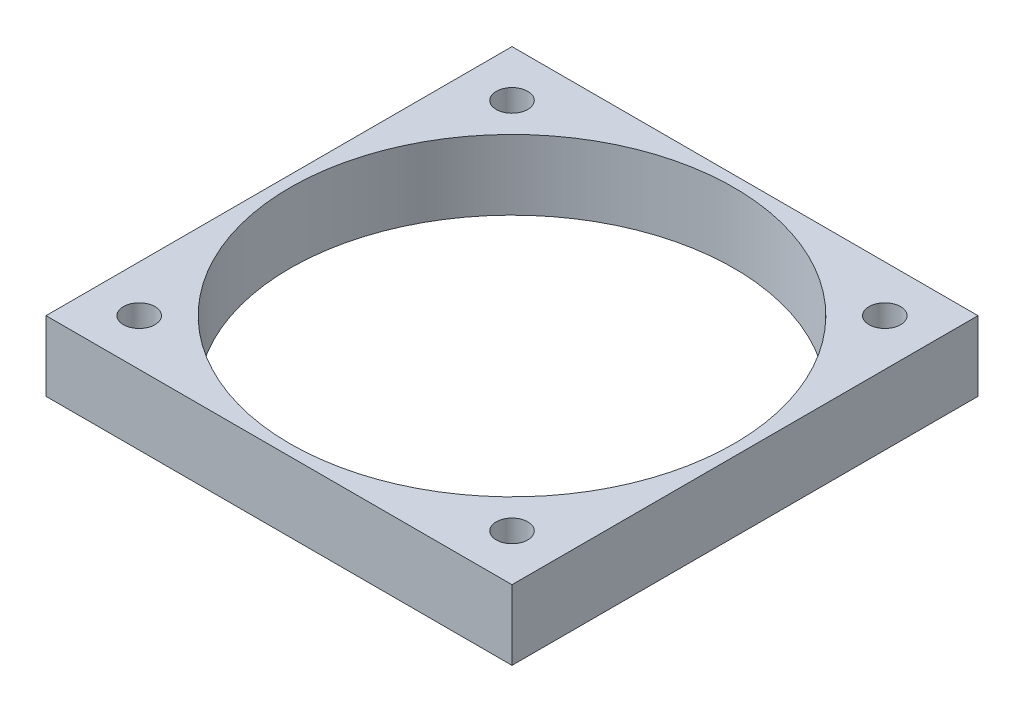
SolidWorks part; units mm, degrees
ref_plane "Front Plane" through (0, 0, 0) normal (0, 0, 1) x (1, 0, 0)
ref_plane "Top Plane" through (0, 0, 0) normal (0, 1, 0) x (1, 0, 0)
ref_plane "Right Plane" through (0, 0, 0) normal (1, 0, 0) x (0, 0, -1)
sketch "Sketch1" plane through (0, 0, 0) normal (0, 1, 0) x (1, 0, 0)
  line L0 (0, 40) -> (40, 0) construction
  line L1 (0, 0) -> (40, 0)
  line L2 (0, 0) -> (0, 40)
  line L3 (0, 40) -> (40, 40)
  line L4 (40, 0) -> (40, 40)
  line L6 (36, 36) -> (4, 36) construction
  line L7 (36, 36) -> (36, 4) construction
  line L8 (36, 4) -> (4, 4) construction
  line L9 (4, 36) -> (4, 4) construction
  line L10 (36, 36) -> (4, 4) construction
  line L11 (36, 4) -> (4, 36) construction
  circle A0 centre (4, 36) radius 1.3526
  circle A1 centre (36, 36) radius 1.3526
  circle A2 centre (4, 4) radius 1.3526
  circle A3 centre (36, 4) radius 1.3526
  circle A4 centre (20, 20) radius 19.05
  point P5 (20, 20)
  dimension "D4" = 38.1
  dimension "D5" = 2.7051
  dimension "D1" = 40
  dimension "D2" = 40
  dimension "D3" = 32
extrude "Boss-Extrude1" add sketch "Sketch1" along normal blind 6
ref_plane "Plane1" through (20, 0, 0) normal (1, 0, 0) x (0, 0, -1)
ref_plane "Plane2" through (0, 0, -20) normal (0, 0, -1) x (-1, 0, 0)
equation "\"D2@Sketch1\"=\"D1@Sketch1\""
